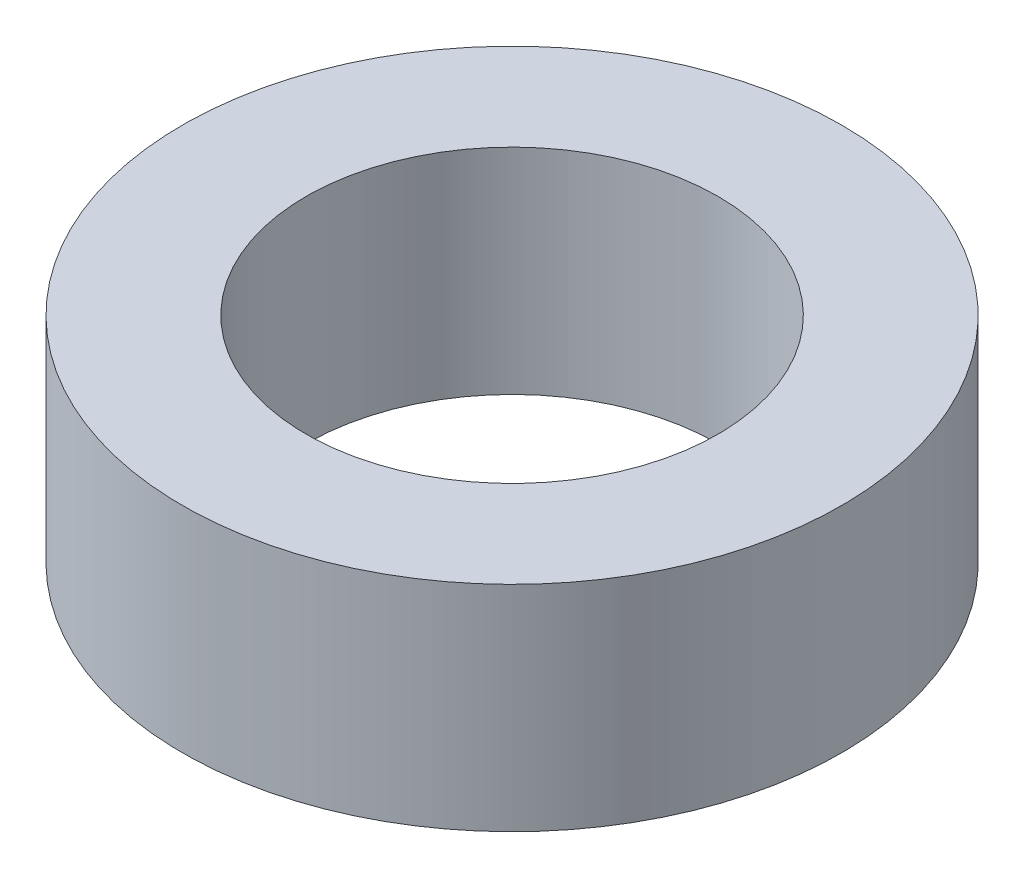
SolidWorks part; units mm, degrees
ref_plane "Front Plane" through (0, 0, 0) normal (0, 0, 1) x (1, 0, 0)
ref_plane "Top Plane" through (0, 0, 0) normal (0, 1, 0) x (1, 0, 0)
ref_plane "Right Plane" through (0, 0, 0) normal (1, 0, 0) x (0, 0, -1)
sketch "Sketch1" plane through (0, 0, 0) normal (0, 1, 0) x (1, 0, 0)
  circle A0 centre (0, 0) radius 20
  dimension "FLANGE_OD" = 40
extrude "Boss-Extrude1" add sketch "Sketch1" along normal blind 13
sketch "Sketch2" plane through (0, 0, 0) normal (0, 1, 0) x (1, 0, 0)
  circle A0 centre (0, 0) radius 12.5
  dimension "BORE_D" = 25
extrude "Cut-Extrude1" cut sketch "Sketch2" along normal through all
sketch "Sketch3" plane through (0, 13, 0) normal (0, 1, 0) x (1, 0, 0)
  circle A0 centre (0, 0) radius 8.0333 construction
  circle A1 centre (-8.0333, 0) radius 1.5
  dimension "BOLT_D" = 3
  dimension "BOLT_PCD" = 16.0667
extrude "Cut-Extrude2" cut sketch "Sketch3" against normal blind 8.0246 rebuild error yes
pattern_circular "CirPattern1" count 8 over 360 rebuild error yes
